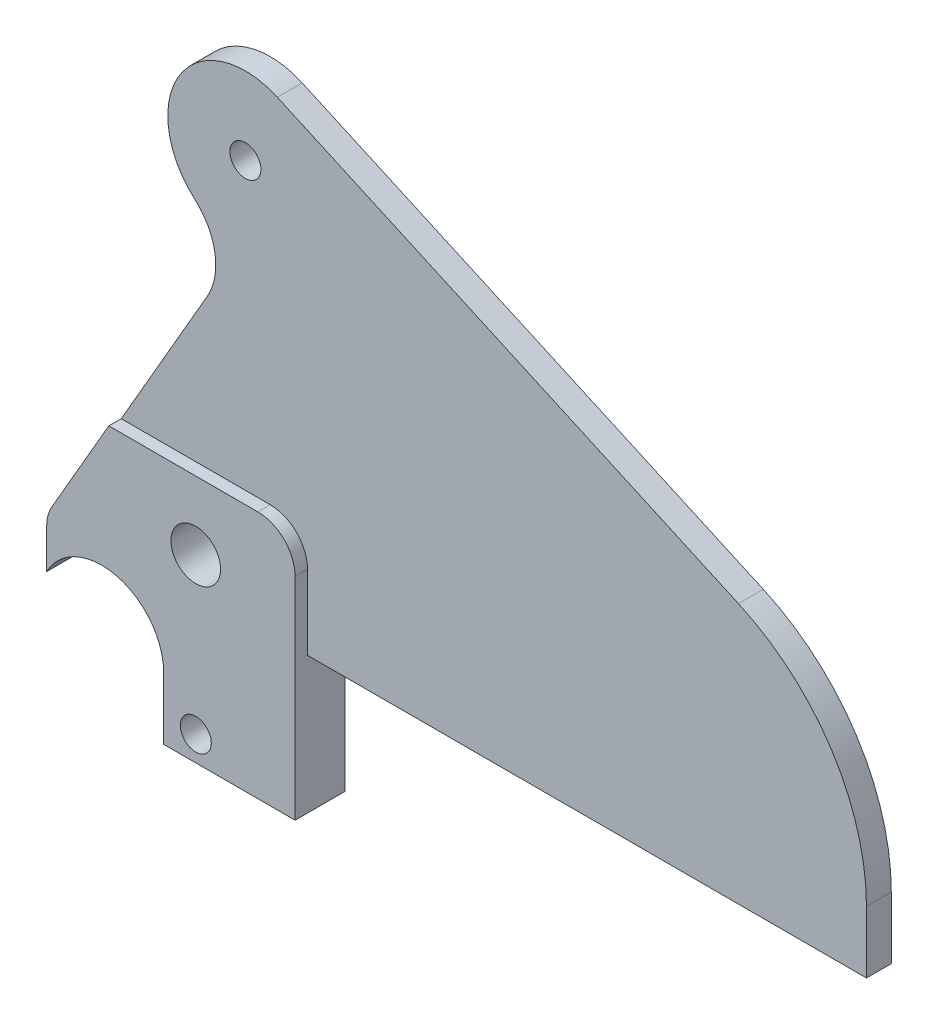
SolidWorks part; units mm, degrees
material "Alloy Steel"
ref_plane "Front Plane" through (0, 0, 0) normal (0, 0, 1) x (1, 0, 0)
ref_plane "Top Plane" through (0, 0, 0) normal (0, 1, 0) x (1, 0, 0)
ref_plane "Right Plane" through (0, 0, 0) normal (1, 0, 0) x (0, 0, -1)
other "Configuration Table"
sketch "Sketch1" plane through (0, 0, 0) normal (0, 0, 1) x (1, 0, 0)
  line L0 (-2.5812, -2) -> (8, -2)
  line L1 (8, -2) -> (8, 18)
  line L2 (8, 18) -> (-7, 18)
  line L3 (-7, 18) -> (-12, 9.3397)
  line L4 (-12, 9.3397) -> (-12, 5.3397)
  line L5 (8, 9) -> (53, 9)
  line L6 (53, 9) -> (53, 14)
  line L7 (5.5697, 46.6973) -> (42.6951, 29.9524)
  line L8 (-7, 18) -> (-0.061, 30.0186)
  line L10 (-2.5812, 3) -> (-2.5812, -2)
  circle A0 centre (0, 0) radius 1.25
  circle A1 centre (0, 12.5) radius 2
  circle A2 centre (3, 41) radius 1.25
  arc A3 (5.5697, 46.6973) -> (-1.1062, 36.2881) centre (3, 41) ccw
  arc A4 (-0.061, 30.0186) -> (-1.1062, 36.2881) centre (-4.3912, 32.5186) ccw
  arc A5 (53, 14) -> (42.6951, 29.9524) centre (35.5, 14) ccw
  arc A7 (-2.5812, 3) -> (-12, 5.3397) centre (-7.5812, 3) ccw
  point P12 (3, 41)
  dimension "D1" = 2.5
  dimension "D2" = 4
  dimension "D15" = 2.5
  dimension "D16" = 12.5
  dimension "D17" = 10
  dimension "D18" = 35
  dimension "D19" = 5
  dimension "D3" = 12.5
  dimension "D4" = 120
  dimension "D5" = 2
  dimension "D6" = 8
  dimension "D7" = 20
  dimension "D8" = 20
  dimension "D9" = 10
  dimension "D10" = 11
  dimension "D11" = 45
  dimension "D12" = 5
  dimension "D13" = 43
  dimension "D14" = 3
  dimension "D20" = 4
  dimension "D21" = 5
extrude "Boss-Extrude1" add sketch "Sketch1" along normal mid plane 2 contours L3 L4 L0 L1 L2 A1 A0 | A4 L8 L2 L1 L5 L6 A3 A2 region at (0.1944, 9.0571, 0) region at (22.283, 24.5779, 0)
extrude "Boss-Extrude2" add sketch "Sketch1<3>" along normal mid plane 4 contours L3 L4 L0 L1 L2 A1 A0 region at (0.1944, 9.0571, 0)
sketch "Sketch1<3>" plane through (0, 0, 0) normal (0, 0, 1) x (1, 0, 0) same geometry as "Sketch1"
fillet "Fillet1" radius 3 3 edges at (-12, 9.3397, 0) (8, 18, -1.5) (8, 18, 1.5)
sketch3d "3DSketch2"
  circle A0 centre (0, 12.5, 2) radius 2 construction
  point P0 (0, 12.5, 0)
  point P3 (0, 12.5, 4)
